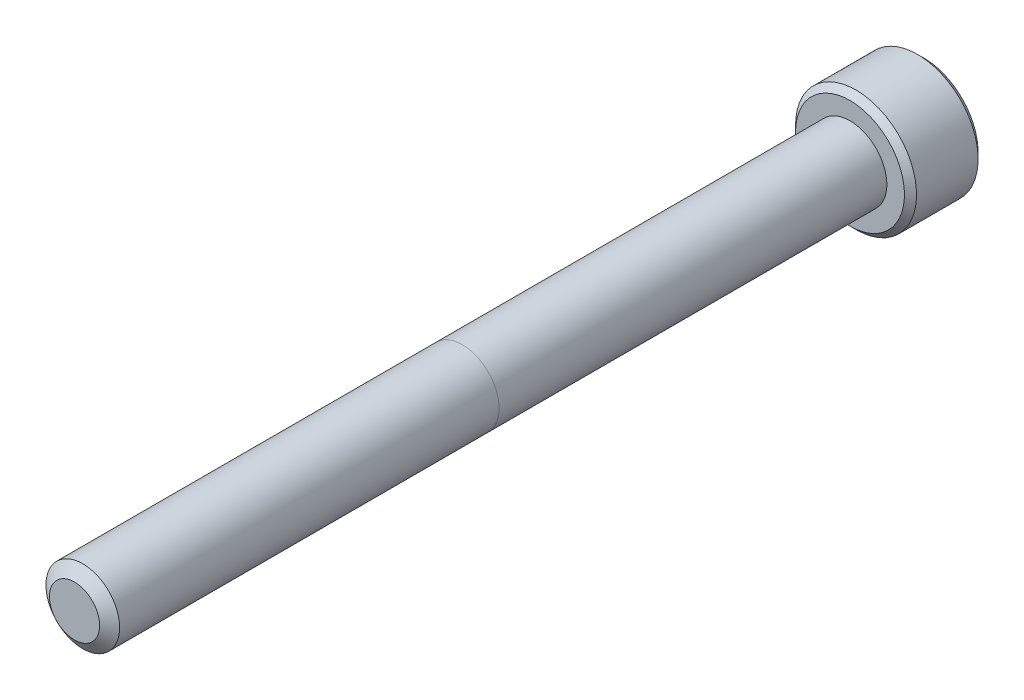
SolidWorks part; units mm, degrees
ref_plane "Front Plane" through (0, 0, 0) normal (0, 0, 1) x (1, 0, 0)
ref_plane "Top Plane" through (0, 0, 0) normal (0, 1, 0) x (1, 0, 0)
ref_plane "Right Plane" through (0, 0, 0) normal (1, 0, 0) x (0, 0, -1)
sketch "Sketch1" plane through (0, 0, 0) normal (0, 0, 1) x (1, 0, 0)
  circle A0 centre (0, 0) radius 2.413
  dimension "OD" = 4.826
extrude "Extrude1" add sketch "Sketch1" against normal blind 50.8
sketch "Sketch2" plane through (0, 0, 0) normal (0, 0, 1) x (1, 0, 0)
  circle A0 centre (0, 0) radius 2.413 construction
  circle A1 centre (0, 0) radius 2.413
curve "Helix/Spiral1" [suppressed] pitch 0.7937 height 51.5938 turns 65 parameters "pitch"=0.7937
sketch "Sketch3" plane through (0, 0, 0) normal (1, 0, 0) x (0, 0, -1)
  line L0 (-0.6945, 2.413) -> (-0.3969, 1.8974)
  line L1 (-0.3969, 1.8974) -> (-0.2977, 1.8974)
  line L2 (-0.2977, 1.8974) -> (0, 2.413)
  line L3 (-0.6945, 2.413) -> (0, 2.413)
  line L4 (-0.3473, 2.413) -> (-0.3473, 1.8974) construction
  line L5 (-0.5457, 2.1552) -> (-0.1488, 2.1552) construction
  line L6 (0, 2.413) -> (0, -2.413) construction
  dimension "D2" = 0.3969
  dimension "D3" = 60
sweep "Cut-Sweep1" [suppressed] cut profiles "Sketch3" path "Helix/Spiral1"
sketch "Sketch4" plane through (0, 0, 0) normal (1, 0, 0) x (0, 0, -1)
  line L0 (0.5388, 2.413) -> (0, 1.6434)
  line L1 (0, 1.6434) -> (0, 2.413)
  line L2 (0.5388, 2.413) -> (0, 2.413)
  line L3 (-0.6945, 2.413) -> (0, 2.413) construction
  line L4 (0, 0) -> (7.0209, 0) construction
  dimension "D1" = 55
  dimension "D2" = 0.254
revolve "Cut-Revolve1" cut sketch "Sketch4" angle 360 about L4
sketch "Sketch5" [suppressed] plane through (0, 0, 0) normal (1, 0, 0) x (0, 0, -1)
  line L0 (50.8, -1.9083) -> (50.8, 1.7217) construction
  line L1 (50.8, 2.54) -> (25.5202, 2.54)
  line L2 (50.8, 2.54) -> (50.8, 0)
  line L3 (50.8, 0) -> (25.4, 0)
  line L4 (25.4, 2.2098) -> (25.4, 0)
  line L5 (25.5202, 2.54) -> (25.4, 2.2098)
  line L6 (0, 0) -> (9.9695, 0) construction
  point P3 (25.4, 2.54)
  point P10 (25.4, 2.54)
  dimension "D1" = 0.3302
  dimension "Thread min" = 25.4
  dimension "D2" = 0.127
  dimension "D3" = 20
revolve "partially thread" [suppressed] add sketch "Sketch5" angle 360 about L6
sketch "Sketch6" plane through (0, 0, -50.8) normal (0, 0, -1) x (-1, 0, 0)
  circle A0 centre (0, 0) radius 3.9624
  dimension "head dia" = 7.9248
extrude "Extrude2" add sketch "Sketch6" along normal blind 4.826
sketch "Sketch7" plane through (0, 0, -55.626) normal (0, 0, -1) x (-1, 0, 0)
  line L1 (0, 2.2914) -> (-1.9844, 1.1457)
  line L2 (-1.9844, 1.1457) -> (-1.9844, -1.1457)
  line L3 (-1.9844, -1.1457) -> (0, -2.2914)
  line L4 (0, -2.2914) -> (1.9844, -1.1457)
  line L5 (1.9844, -1.1457) -> (1.9844, 1.1457)
  line L6 (1.9844, 1.1457) -> (0, 2.2914)
  circle A0 centre (0, 0) radius 1.9844 construction
  dimension "hex dia" = 3.9688
extrude "Cut-Extrude1" cut sketch "Sketch7" against normal blind 2.9766
sketch "Sketch8" plane through (0, 0, -55.626) normal (0, 0, -1) x (-1, 0, 0)
  circle A0 centre (0, 0) radius 2.2914
extrude "Cut-Extrude2" cut sketch "Sketch8" against normal through all draft 45
chamfer "Chamfer1" distance 0.3962 angle 45 2 edges at (-3.9624, 0, -55.626) (-3.9624, 0, -50.8)
sketch "Sketch10" plane through (0, 0, 0) normal (0, 1, 0) x (1, 0, 0)
  line L0 (-2.413, 25.4) -> (2.413, 25.4)
  line L1 (-2.413, 50.8) -> (-2.413, 0.5388) construction
  line L2 (2.413, 0.5388) -> (2.413, 50.8) construction
  line L3 (-1.6434, 0) -> (1.6434, 0) construction
  dimension "D1" = 25.4
split line "Split Line2"
equation "\"D3@Helix/Spiral1\" = \"screw length@Extrude1\"+\"pitch@Helix/Spiral1\""
equation "\"D1@Sketch3\" = \"pitch@Helix/Spiral1\"*.125"
equation "\"D2@Sketch3\" = \"pitch@Helix/Spiral1\"*.5"
equation "\"D1@Cut-Extrude1\" = \"hex dia@Sketch7\"*.75"
equation "\"D1@Chamfer1\" = \"head dia@Sketch6\"*.05"
